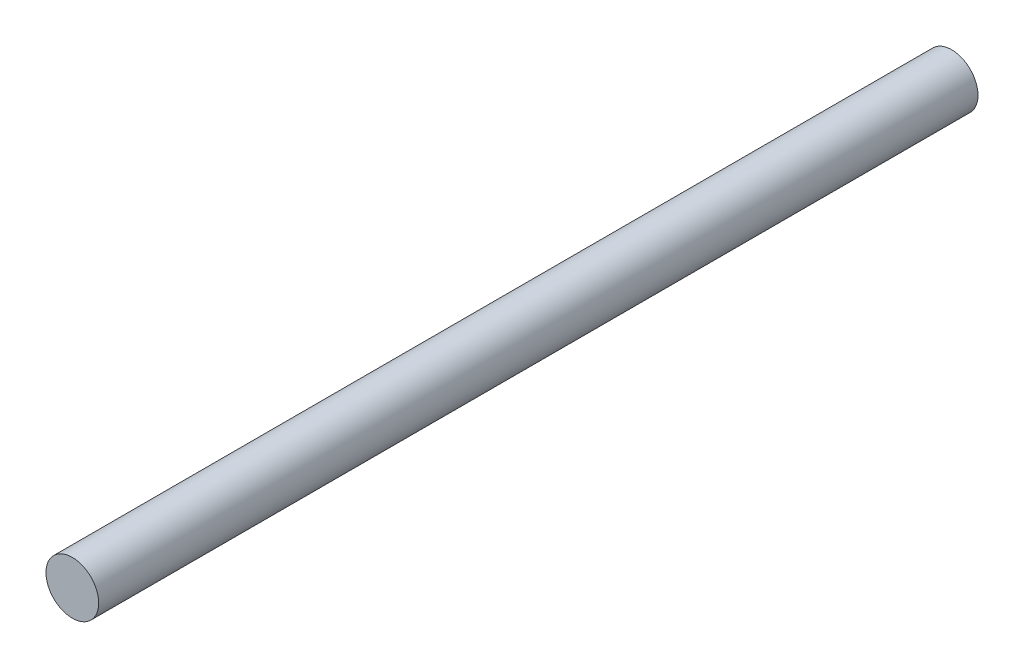
SolidWorks part; units mm, degrees
ref_plane "Front Plane" through (0, 0, 0) normal (0, 0, 1) x (1, 0, 0)
ref_plane "Top Plane" through (0, 0, 0) normal (0, 1, 0) x (1, 0, 0)
ref_plane "Right Plane" through (0, 0, 0) normal (1, 0, 0) x (0, 0, -1)
sketch "Sketch1" plane through (0, 0, 0) normal (0, 0, 1) x (1, 0, 0)
  circle A0 centre (0, 0) radius 3
  dimension "D1" = 6
extrude "Boss-Extrude1" add sketch "Sketch1" along normal blind 50 and the other way blind 50
